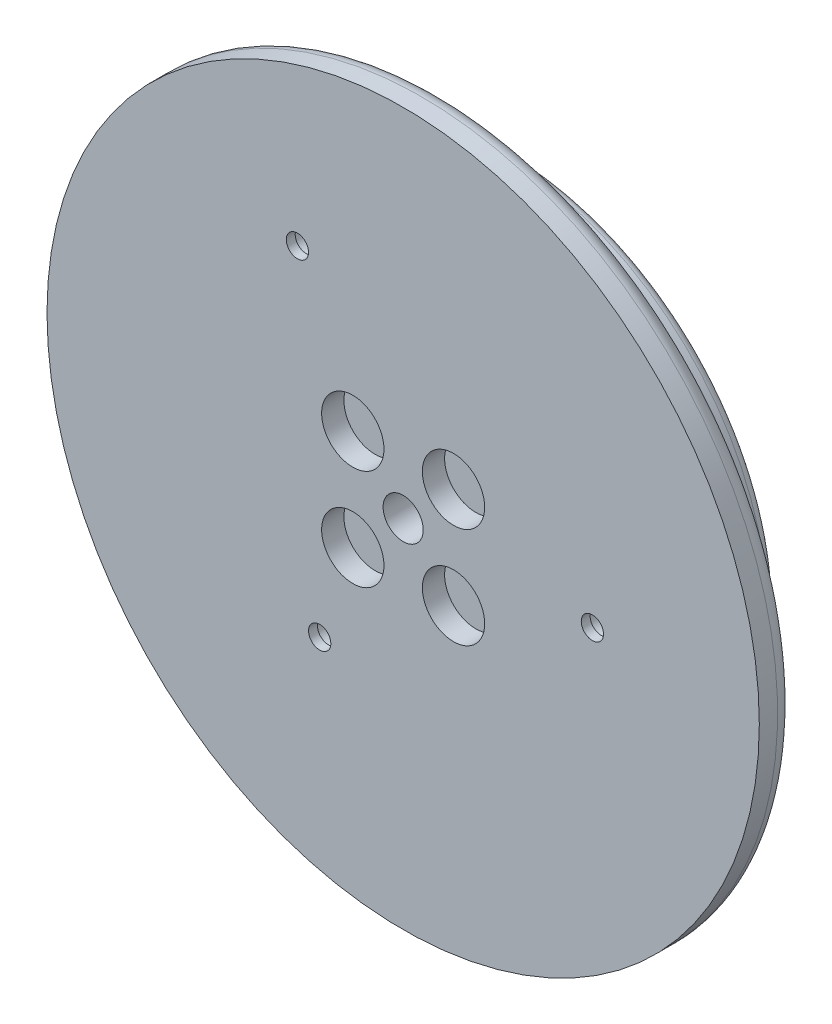
SolidWorks part; units mm, degrees
other "Main Coupler Piece"
other "back piece"
other "insert1"
other "insert2"
other "insert3"
ref_plane "Front Plane" through (0, 0, 0) normal (0, 0, 1) x (1, 0, 0)
ref_plane "Top Plane" through (0, 0, 0) normal (0, 1, 0) x (1, 0, 0)
ref_plane "Right Plane" through (0, 0, 0) normal (1, 0, 0) x (0, 0, -1)
sketch "Sketch1" plane through (0, 0, 0) normal (0, 0, 1) x (1, 0, 0)
  circle A0 centre (0, 0) radius 12.5
  circle A1 centre (0, 0) radius 30
  dimension "D1" = 25
  dimension "D2" = 60
extrude "Boss-Extrude1" add sketch "Sketch1" along normal blind 6
sketch "Sketch2" plane through (0, 0, 6) normal (0, 0, 1) x (1, 0, 0)
  line L1 (-5.656, 5.6577) -> (5.656, 5.6577) construction
  line L2 (-5.656, 5.6577) -> (-5.656, -5.6577) construction
  line L3 (-5.656, -5.6577) -> (5.656, -5.6577) construction
  line L4 (5.656, 5.6577) -> (5.656, -5.6577) construction
  circle A0 centre (0, 0) radius 2.25
  circle A1 centre (-5.656, 5.6577) radius 1.5
  circle A2 centre (-5.656, -5.6577) radius 1.5
  circle A3 centre (5.656, -5.6577) radius 1.5
  circle A4 centre (5.656, 5.6577) radius 1.5
  circle A5 centre (0, 0) radius 40
  point P15 (0, -5.6577)
  point P16 (-5.656, 0)
  dimension "D1" = 4.5
  dimension "D4" = 3
  dimension "D5" = 80
  dimension "D2" = 16
  dimension "D3" = 11.3154
extrude "Boss-Extrude2" add sketch "Sketch2" along normal blind 4
sketch "Sketch3" plane through (0, 0, 10) normal (0, 0, 1) x (1, 0, 0)
  circle A0 centre (-5.656, 5.6577) radius 3.5
  circle A1 centre (5.656, 5.6577) radius 3.5
  circle A2 centre (5.656, -5.6577) radius 3.5
  circle A3 centre (-5.656, -5.6577) radius 3.5
  dimension "D1" = 7
extrude "Cut-Extrude1" cut sketch "Sketch3" against normal blind 2.5
sketch "Sketch4" plane through (0, 0, 0) normal (0, 0, -1) x (-1, 0, 0)
  circle A0 centre (-20, 0) radius 5.15
  circle A1 centre (0, -20) radius 5.15
  circle A2 centre (0, 0) radius 20 construction
  circle A3 centre (0, 0) radius 20 construction
  circle A4 centre (20, 0) radius 5.15
  circle A5 centre (0, 0) radius 20 construction
  circle A6 centre (0, 20) radius 5.15
  circle A7 centre (0, 0) radius 20 construction
  circle A8 centre (0, 20) radius 2.65 construction
  circle A9 centre (14.1421, 14.1421) radius 2.65
  circle A10 centre (0, 0) radius 20 construction
  circle A11 centre (20, 0) radius 2.65 construction
  circle A12 centre (0, 0) radius 20 construction
  circle A13 centre (14.1421, -14.1421) radius 2.65
  circle A14 centre (0, 0) radius 20 construction
  circle A15 centre (0, -20) radius 2.65 construction
  circle A16 centre (0, 0) radius 20 construction
  circle A17 centre (-14.1421, -14.1421) radius 2.65
  circle A18 centre (0, 0) radius 20 construction
  circle A19 centre (-20, 0) radius 2.65 construction
  circle A20 centre (0, 0) radius 20 construction
  circle A21 centre (-14.1421, 14.1421) radius 2.65
  circle A22 centre (0, 0) radius 20 construction
  point P17 (0, 0)
  point P39 (0, 0)
  dimension "D1" = 10.3
  dimension "D2" = 40
  dimension "D4" = 5.3
  dimension "D3" = 4
  dimension "D5" = 8
extrude "Cut-Extrude2" cut sketch "Sketch4" against normal blind 3 contours A4
sketch "Sketch5" plane through (0, 0, 7.5) normal (0, 0, 1) x (1, 0, 0)
  circle A0 centre (-5.656, 5.6577) radius 3.5
  circle A1 centre (5.656, 5.6577) radius 3.5
  circle A2 centre (-5.656, -5.6577) radius 3.5
  circle A3 centre (5.656, -5.6577) radius 3.5
extrude "Boss-Extrude3" add sketch "Sketch5" against normal blind 0.2
sketch "Sketch6" plane through (0, 0, 0) normal (0, 0, -1) x (-1, 0, 0)
  line L0 (0, 0) -> (20, 34.641) construction
  line L1 (0, 0) -> (20, -34.641) construction
  circle A0 centre (-21.25, 0) radius 1.25
  circle A1 centre (0, 0) radius 12.5 construction
  circle A2 centre (10.625, 18.403) radius 1.25 construction
  circle A3 centre (10.625, -18.403) radius 1.25 construction
  circle A4 centre (0, 0) radius 30 construction
  circle A5 centre (-34.2276, 0) radius 2.5 construction
  circle A6 centre (0, 0) radius 40 construction
  circle A7 centre (11.875, 20.5681) radius 1.25
  circle A8 centre (9.375, -16.238) radius 1.25
  point P12 (0, 0)
  point P24 (0, 0)
  point P25 (0, 0)
  point P26 (8.6816, -15.0369)
  dimension "D1" = 21.25
  dimension "D2" = 2.5
  dimension "D4" = 5
  dimension "D5" = 2.5
  dimension "D6" = 2.5
  dimension "D3" = 3
extrude "Cut-Extrude3" cut sketch "Sketch6" against normal blind 10
sketch "Sketch7" plane through (0, 0, 0) normal (0, 0, -1) x (-1, 0, 0)
  line L0 (0, 0) -> (20, 34.641) construction
  line L1 (0, 0) -> (20, -34.641) construction
  circle A0 centre (-21.25, 0) radius 3.125
  circle A3 centre (0, 0) radius 40 construction
  circle A4 centre (11.875, 20.5681) radius 3.125
  circle A5 centre (9.375, -16.238) radius 3.125
  circle A6 centre (9.375, -16.238) radius 1.25 construction
  circle A7 centre (11.875, 20.5681) radius 1.25 construction
  circle A8 centre (-21.25, 0) radius 1.25 construction
  point P3 (0, 0)
  point P4 (0, 0)
  point P6 (0, 0)
  point P19 (0, 0)
  point P24 (0, 0)
  point P25 (0, 0)
  point P26 (0, 0)
  point P29 (0, 0)
  dimension "D1" = 6.25
extrude "Cut-Extrude4" cut sketch "Sketch7" against normal offset from surface (9 mm away) 1 contours A5 | A4 | A0 up to face at (20, 0, 10)
sketch "Sketch8" plane through (0, 0, 0) normal (0, 0, -1) x (-1, 0, 0)
  circle A0 centre (20, 0) radius 2
  circle A1 centre (20, 0) radius 5.15 construction
  circle A2 centre (-10, -17.3205) radius 2
  circle A3 centre (-10, 17.3205) radius 2
  circle A4 centre (0, 0) radius 30 construction
  circle A5 centre (17.3205, -10) radius 2
  circle A6 centre (10, -17.3205) radius 2
  circle A7 centre (0, -20) radius 2
  circle A8 centre (-10, -17.3205) radius 2
  circle A9 centre (-17.3205, -10) radius 2
  circle A10 centre (-20, 0) radius 2
  circle A11 centre (-17.3205, 10) radius 2
  circle A12 centre (-10, 17.3205) radius 2
  circle A13 centre (0, 20) radius 2
  circle A14 centre (10, 17.3205) radius 2
  circle A15 centre (17.3205, 10) radius 2
  circle A16 centre (0, 0) radius 30 construction
  point P11 (0, 0)
  point P36 (0, 0)
  dimension "D1" = 4
  dimension "D2" = 3
  dimension "D3" = 12
extrude "Cut-Extrude5" cut sketch "Sketch8" against normal offset from surface (8 mm away) 2 contours A11 | A9 | A15 | A5 | A13 | A7 | A3 | A2 up to face at (20, 0, 10)
sketch "Sketch10" plane through (0, 0, 0) normal (0, 0, -1) x (-1, 0, 0)
  circle A0 centre (20, 0) radius 5.15
  circle A5 centre (-10, 17.3205) radius 2
  circle A6 centre (-10, -17.3205) radius 2
  circle A7 centre (20, 0) radius 5.15 construction
  circle A8 centre (-17.3205, 10) radius 2
  circle A9 centre (0, 20) radius 2
  circle A10 centre (17.3205, 10) radius 2
  circle A11 centre (17.3205, -10) radius 2
  circle A12 centre (0, -20) radius 2
  circle A13 centre (-17.3205, -10) radius 2
  circle A16 centre (20, 0) radius 5.15
  circle A17 centre (0, 0) radius 30
  circle A18 centre (0, 0) radius 12.5
  circle A19 centre (20, 0) radius 5.15
  circle A20 centre (0, 0) radius 30 construction
  circle A21 centre (0, 0) radius 20 construction
  circle A22 centre (-10, -17.3205) radius 2 construction
  circle A23 centre (-10, 17.3205) radius 2 construction
  point P13 (0, 0)
  point P14 (0, 0)
  point P38 (0, 0)
  dimension "D1" = 25
  dimension "D2" = 4
sketch "Sketch11" plane through (0, 0, 9) normal (0, 0, -1) x (-1, 0, 0)
  circle A0 centre (-21.25, 0) radius 3
  circle A1 centre (11.875, 20.5681) radius 3
  circle A2 centre (9.375, -16.238) radius 3
  circle A3 centre (9.375, -16.238) radius 3.125 construction
  circle A4 centre (-21.25, 0) radius 1.5
  circle A5 centre (11.875, 20.5681) radius 1.5
  circle A6 centre (9.375, -16.238) radius 1.5
  circle A7 centre (11.875, 20.5681) radius 3.125 construction
  point P12 (0, 0)
  point P13 (0, 0)
  dimension "D1" = 6
  dimension "D2" = 3
extrude "Boss-Extrude6" add sketch "Sketch11" along normal blind 3 separate body
extrude "Boss-Extrude7" add sketch "Sketch10" along normal blind 1.2 separate body
fillet "Fillet1" radius 10 1 edges at (30, 0, 6)
fillet "Fillet2" radius 2 1 edges at (40, 0, 6)
sketch "Sketch12" plane through (0, 0, 6) normal (0, 0, -1) x (-1, 0, 0)
  circle A0 centre (0, 0) radius 12.5
  circle A1 centre (0, 0) radius 2.25
  circle A2 centre (-5.656, 5.6577) radius 1.5
  circle A3 centre (5.656, 5.6577) radius 1.5
  circle A4 centre (5.656, -5.6577) radius 1.5
  circle A5 centre (-5.656, -5.6577) radius 1.5
extrude "Boss-Extrude8" add sketch "Sketch12" along normal blind 2
sketch "Sketch15" plane through (0, 0, -1.2) normal (0, 0, -1) x (-1, 0, 0)
  line L0 (0, 0) -> (-28, 0) construction
  line L1 (-27.9821, 1) -> (-12.4599, 1)
  line L2 (-27.9821, -1) -> (-12.4599, -1)
  line L3 (14.8571, 23.7332) -> (7.096, 10.2906)
  line L4 (13.125, 24.7332) -> (5.3639, 11.2906)
  line L5 (13.125, -24.7332) -> (5.3639, -11.2906)
  line L6 (14.8571, -23.7332) -> (7.096, -10.2906)
  circle A0 centre (0, 0) radius 28
  circle A1 centre (0, 0) radius 30
  circle A2 centre (0, 0) radius 30 construction
  circle A3 centre (0, 0) radius 12.5 construction
  circle A4 centre (0, 0) radius 12.5
  circle A5 centre (0, 0) radius 12.5 construction
  point P27 (0, 0)
  circle M7 centre (0, 0) radius 12.5
  circle M17 centre (0, 0) radius 30
  dimension "D1" = 2
  dimension "D2" = 1
  dimension "D3" = 1
  dimension "D4" = 3
extrude "Boss-Extrude10" add sketch "Sketch15" along normal blind 0.75 contours A0 M17 | L3 A0 L4 M7 | L5 A0 L6 M7 | L0 A0 L2 M7 | L0 A4 L1 A0
fillet "Fillet5" radius 1 1 edges at (-30, 0, -1.95)
fillet "Fillet6" radius 0.25 12 edges at (20.221, 1, -1.95) (27.9821, 1, -1.575) (14, 24.2487, -1.95) (-13.125, 24.7332, -1.575) (14, 24.2487, -1.2) (-10.9765, 17.0119, -1.95) (-28, 0, -1.95) (-10.9765, -17.0119, -1.95) (-9.2445, -18.0119, -1.95) (14, -24.2487, -1.95) (20.221, -1, -1.2) (-9.2445, 18.0119, -1.95)
